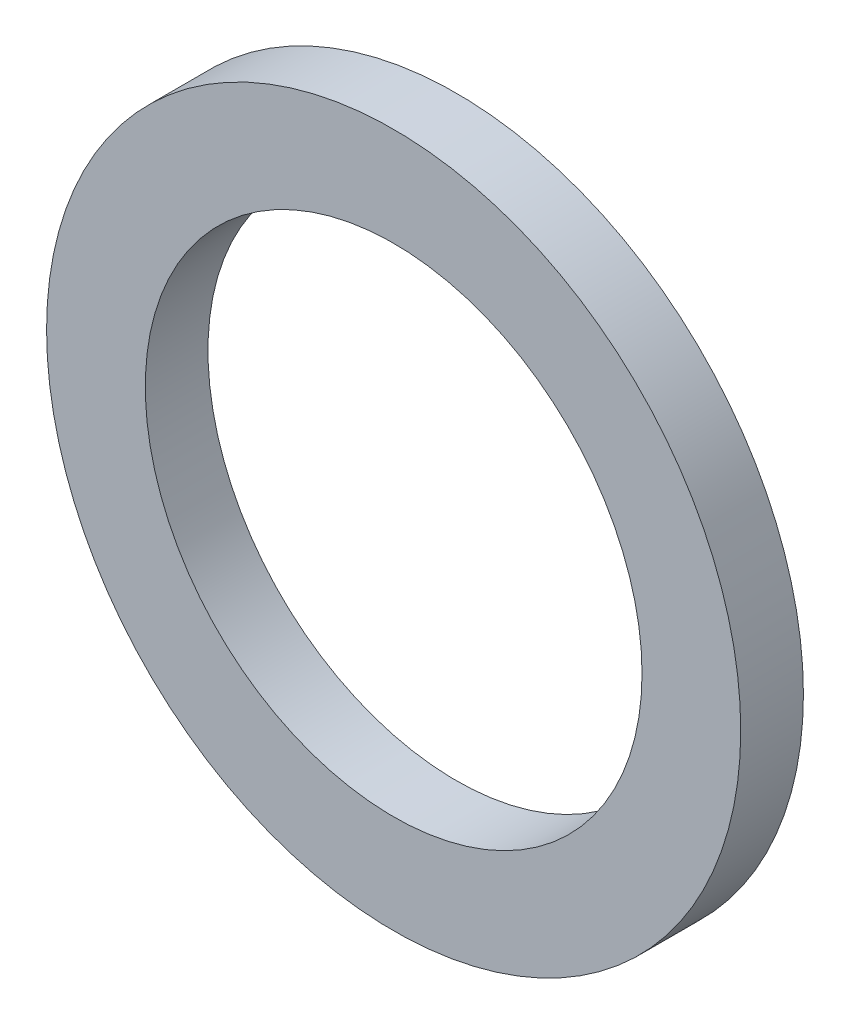
SolidWorks part; units mm, degrees
ref_plane "Front Plane" through (0, 0, 0) normal (0, 0, 1) x (1, 0, 0)
ref_plane "Top Plane" through (0, 0, 0) normal (0, 1, 0) x (1, 0, 0)
ref_plane "Right Plane" through (0, 0, 0) normal (1, 0, 0) x (0, 0, -1)
sketch "Sketch1" plane through (0, 0, 0) normal (0, 0, 1) x (1, 0, 0)
  circle A0 centre (0, 0) radius 15.85
  circle A1 centre (0, 0) radius 22.15
extrude "Boss-Extrude1" add sketch "Sketch1" along normal blind 4
